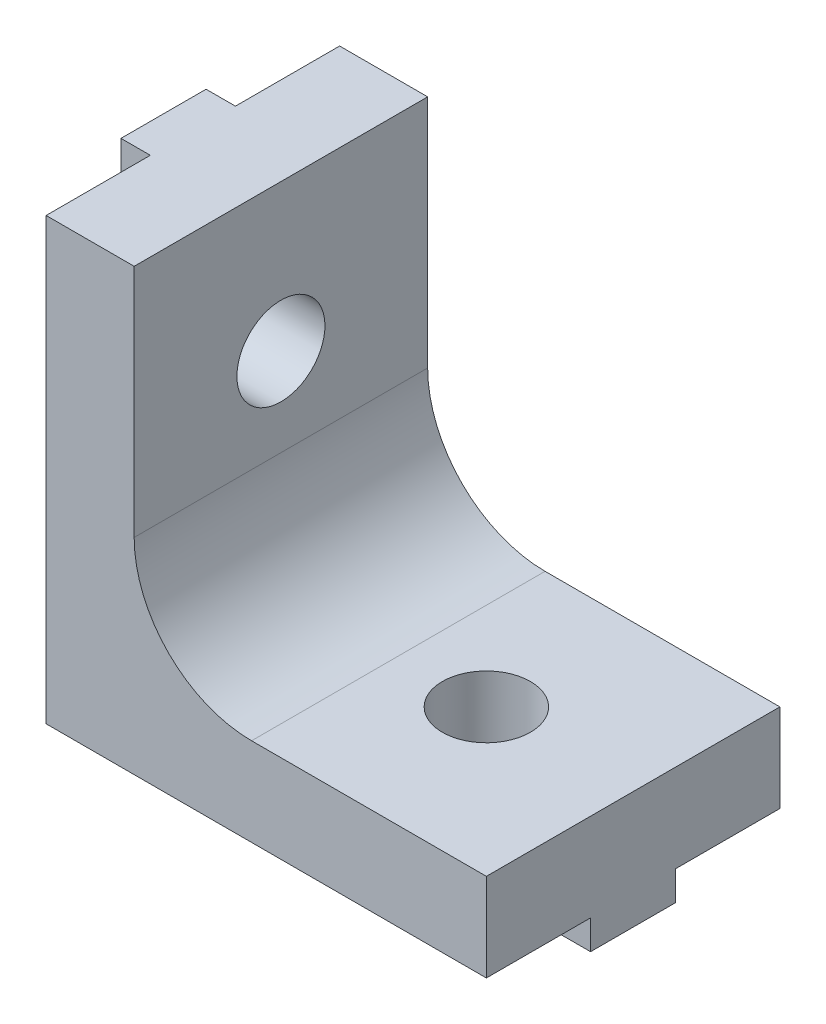
SolidWorks part; units mm, degrees
ref_plane "Front Plane" through (0, 0, 0) normal (0, 0, 1) x (1, 0, 0)
ref_plane "Top Plane" through (0, 0, 0) normal (0, 1, 0) x (1, 0, 0)
ref_plane "Right Plane" through (0, 0, 0) normal (1, 0, 0) x (0, 0, -1)
sketch "Esquisse1" plane through (0, 0, 0) normal (0, 0, 1) x (1, 0, 0)
  line L0 (0, 0) -> (15, 0)
  line L1 (15, 0) -> (15, 3)
  line L2 (15, 3) -> (7, 3)
  line L4 (3, 7) -> (3, 15)
  line L5 (3, 15) -> (0, 15)
  line L6 (0, 15) -> (0, 0)
  arc A0 (7, 3) -> (3, 7) centre (7, 7) cw
  dimension "D1" = 4
  dimension "D2" = 15
  dimension "D3" = 3
extrude "Boss.-Extru.1" add sketch "Esquisse1" along normal blind 10
sketch "Esquisse4" plane through (0, 0, 0) normal (-1, 0, 0) x (0, 0, 1)
  line L0 (10, 15) -> (0, 15) construction
  line L1 (3.55, 15) -> (6.45, 15)
  line L2 (3.55, 15) -> (3.55, 0)
  line L3 (3.55, 0) -> (6.45, 0)
  line L4 (6.45, 15) -> (6.45, 0)
  line L5 (10, 0) -> (0, 0) construction
  point P8 (5, 15)
  point P9 (5, 15)
  dimension "D1" = 2.9
extrude "Boss.-Extru.2" add sketch "Esquisse4" along normal blind 1
sketch "Esquisse2" plane through (0, 0, 0) normal (-1, 0, 0) x (0, 0, 1)
  line L0 (10, 15) -> (6.45, 15) construction
  line L1 (10, 15) -> (0, 15) construction
  circle A0 centre (5, 10) radius 1.5
  point P6 (0, 0)
  point P9 (5, 15)
  dimension "D1" = 3
  dimension "D2" = 5
extrude "Enlèv. mat.-Extru.1" cut sketch "Esquisse2" against normal through all both and the other way through all
sketch "Esquisse5" plane through (0, 0, 0) normal (0, -1, 0) x (-1, 0, 0)
  line L0 (-15, -10) -> (-15, 0) construction
  line L1 (0, -3.55) -> (-15, -3.55)
  line L2 (0, -3.55) -> (0, -6.45)
  line L3 (0, -6.45) -> (-15, -6.45)
  line L4 (-15, -3.55) -> (-15, -6.45)
  line L5 (1, -6.45) -> (0, -6.45) construction
  point P7 (0, 0)
extrude "Boss.-Extru.3" add sketch "Esquisse5" along normal blind 1
sketch "Esquisse3" plane through (0, 0, 0) normal (0, -1, 0) x (1, 0, 0)
  line L0 (15, 10) -> (15, 6.45) construction
  line L1 (0, 6.45) -> (0, 3.55) construction
  circle A0 centre (10, 5) radius 1.5
  point P6 (15, 8.225)
  point P7 (0, 0)
  point P8 (0, 0)
  point P9 (10, 4.5957)
  point P12 (0, 5)
  dimension "D2" = 5
extrude "Enlèv. mat.-Extru.2" cut sketch "Esquisse3" against normal through all both and the other way through all
